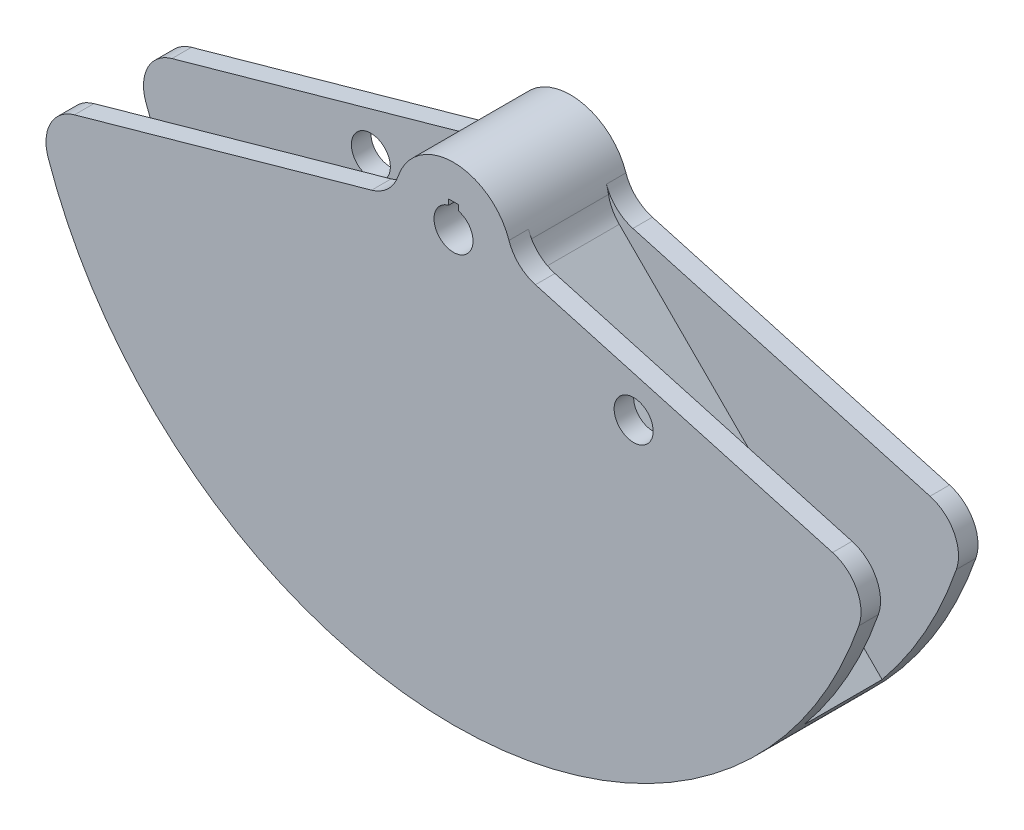
SolidWorks part; units mm, degrees
material "AISI 1020"
ref_plane "Front Plane" through (0, 0, 0) normal (0, 0, 1) x (1, 0, 0)
ref_plane "Top Plane" through (0, 0, 0) normal (0, 1, 0) x (1, 0, 0)
ref_plane "Right Plane" through (0, 0, 0) normal (1, 0, 0) x (0, 0, -1)
other "Center of Mass"
sketch "Sketch1" plane through (0, 0, 0) normal (0, 0, 1) x (1, 0, 0)
  line L0 (-215.6951, -177.5951) -> (-44.4734, -6.3734)
  line L1 (-38.1, 0) -> (38.1, 0) construction
  line L2 (44.4734, -6.3734) -> (215.6951, -177.5951)
  line L3 (0, 0) -> (-117.3327, -48.6008) construction
  line L4 (0, 0) -> (0, -279.4) construction
  line L5 (117.3327, -48.6008) -> (0, 0) construction
  arc A0 (-215.6951, -177.5951) -> (215.6951, -177.5951) centre (0, 0) ccw
  circle A1 centre (0, 0) radius 127 construction
  circle A2 centre (0, 0) radius 12.7
  arc A3 (37.4603, 6.9523) -> (-37.4603, 6.9523) centre (0, 0) ccw
  circle A4 centre (-117.3327, -48.6008) radius 12.7 construction
  circle A5 centre (117.3327, -48.6008) radius 12.7 construction
  arc A6 (44.4734, -6.3734) -> (37.4603, 6.9523) centre (62.4339, 11.5872) cw
  arc A7 (-44.4734, -6.3734) -> (-37.4603, 6.9523) centre (-62.4339, 11.5872) ccw
  dimension "D1" = 558.8
  dimension "D2" = 254
  dimension "D3" = 25.4
  dimension "D4" = 25.4
  dimension "D5" = 25.4
  dimension "D8" = 25.4
  dimension "D6" = 135
  dimension "D7" = 67.5
  dimension "D9" = 90
extrude "Boss-Extrude1" add sketch "Sketch1" along normal mid plane 50.8
sketch "Sketch5" plane through (0, 0, 25.4) normal (0, 0, 1) x (1, 0, 0)
  line L0 (-246.9092, -58.5606) -> (-53.3494, -4.2767)
  line L1 (-38.1, 0) -> (38.1, 0) construction
  line L2 (53.3494, -4.2767) -> (246.9092, -58.5606)
  line L3 (0, 0) -> (-117.3327, -48.6008) construction
  line L4 (0, 0) -> (0, -279.4) construction
  line L5 (117.3327, -48.6008) -> (0, 0) construction
  arc A0 (-264.0554, -91.3187) -> (264.0554, -91.3187) centre (0, 0) ccw
  circle A1 centre (0, 0) radius 127 construction
  circle A2 centre (0, 0) radius 12.7
  arc A3 (36.1249, 12.1078) -> (-36.1249, 12.1078) centre (0, 0) ccw
  circle A4 centre (-117.3327, -48.6008) radius 12.7 construction
  circle A5 centre (117.3327, -48.6008) radius 12.7
  arc A6 (53.3494, -4.2767) -> (36.1249, 12.1078) centre (60.2082, 20.1797) cw
  arc A7 (-53.3494, -4.2767) -> (-36.1249, 12.1078) centre (-60.2082, 20.1797) ccw
  arc A8 (-246.9092, -58.5606) -> (-264.0554, -91.3187) centre (-240.0504, -83.017) ccw
  arc A9 (246.9092, -58.5606) -> (264.0554, -91.3187) centre (240.0504, -83.017) cw
  dimension "D1" = 558.8
  dimension "D2" = 254
  dimension "D3" = 25.4
  dimension "D5" = 25.4
  dimension "D8" = 25.4
  dimension "D4" = 25.4
  dimension "D10" = 25.4
  dimension "D6" = 135
  dimension "D7" = 67.5
  dimension "D9" = 25.4
extrude "Boss-Extrude2" add sketch "Sketch5" along normal blind 12.7
sketch "Sketch6" plane through (0, 0, -25.4) normal (0, 0, -1) x (-1, 0, 0)
  line L0 (-246.9092, -58.5606) -> (-53.3494, -4.2767)
  line L1 (-38.1, 0) -> (38.1, 0) construction
  line L2 (53.3494, -4.2767) -> (246.9092, -58.5606)
  line L3 (0, 0) -> (-117.3327, -48.6008) construction
  line L4 (0, 0) -> (0, -279.4) construction
  line L5 (117.3327, -48.6008) -> (0, 0) construction
  arc A0 (-264.0554, -91.3187) -> (264.0554, -91.3187) centre (0, 0) ccw
  circle A1 centre (0, 0) radius 127 construction
  circle A2 centre (0, 0) radius 12.7
  arc A3 (36.1249, 12.1078) -> (-36.1249, 12.1078) centre (0, 0) ccw
  circle A4 centre (-117.3327, -48.6008) radius 12.7 construction
  circle A5 centre (117.3327, -48.6008) radius 12.7
  arc A6 (53.3494, -4.2767) -> (36.1249, 12.1078) centre (60.2082, 20.1797) cw
  arc A7 (-53.3494, -4.2767) -> (-36.1249, 12.1078) centre (-60.2082, 20.1797) ccw
  arc A8 (246.9092, -58.5606) -> (264.0554, -91.3187) centre (240.0504, -83.017) cw
  arc A9 (-246.9092, -58.5606) -> (-264.0554, -91.3187) centre (-240.0504, -83.017) ccw
  dimension "D1" = 558.8
  dimension "D2" = 254
  dimension "D3" = 25.4
  dimension "D4" = 25.4
  dimension "D7" = 25.4
  dimension "D9" = 25.4
  dimension "D10" = 25.4
  dimension "D5" = 135
  dimension "D6" = 67.5
  dimension "D8" = 25.4
extrude "Boss-Extrude4" add sketch "Sketch6" along normal blind 12.7
sketch "Sketch8" plane through (0, 0, 0) normal (0, 0, 1) x (1, 0, 0)
  line L0 (0, 0) -> (0, 12.7) construction
  line L2 (3.175, 9.525) -> (-3.175, 9.525)
  line L3 (3.175, 9.525) -> (3.175, 15.875)
  line L4 (3.175, 15.875) -> (-3.175, 15.875)
  line L5 (-3.175, 9.525) -> (-3.175, 15.875)
  line L6 (3.175, 9.525) -> (-3.175, 15.875) construction
  line L7 (3.175, 15.875) -> (-3.175, 9.525) construction
  circle A0 centre (0, 0) radius 12.7 construction
  arc A1 (3.175, 12.2967) -> (-3.175, 12.2967) centre (0, 0) ccw
  dimension "D1" = 6.35
  dimension "D2" = 6.35
extrude "Cut-Extrude1" cut sketch "Sketch8" against normal through all both and the other way through all contours L3 L4 L5 L2
